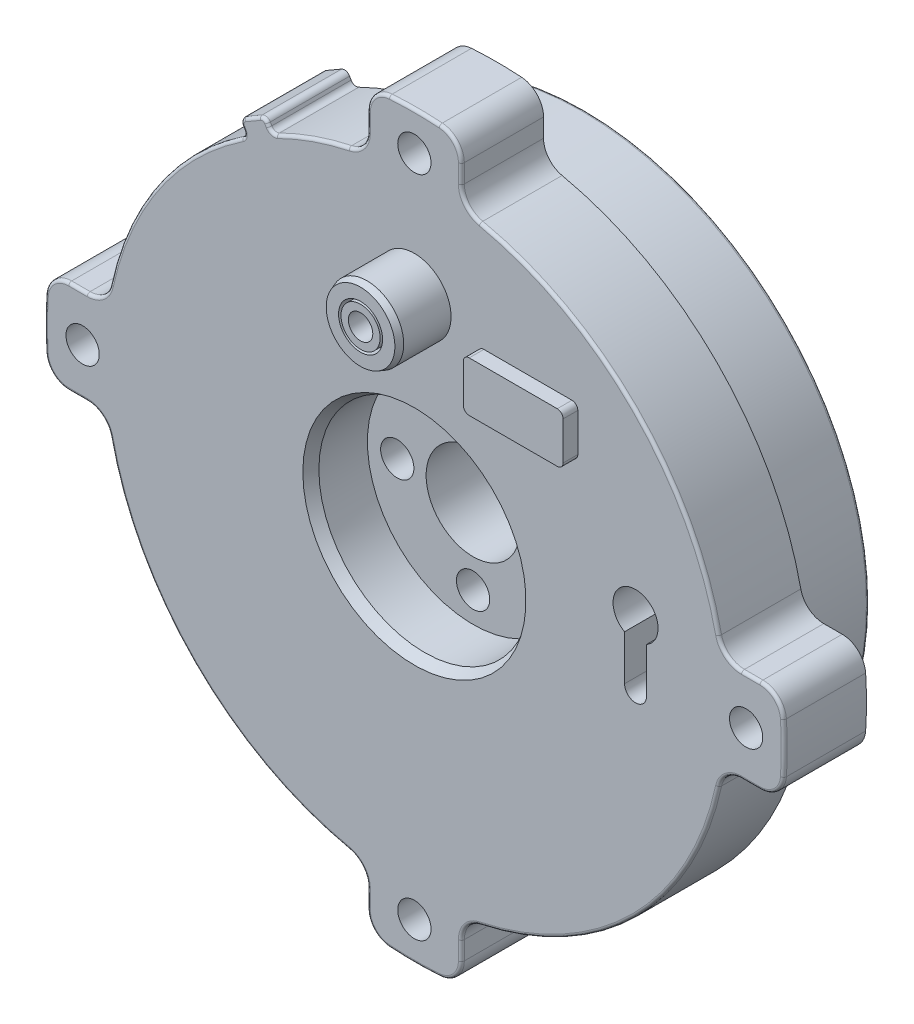
SolidWorks part; units mm, degrees
note: The reader was unsure of these and kept them because the rebuilt part matched: shared geometry of "草图4<7>", "草图4<3>".
other "l7r主轴" parameters "D2"=11, "D1"=38, "D3"=10, "D4"=11, "D5"=20, "D6"=5.8774, "D7"=5.7465, "D8"=5, "D9"=7, "D10"=8, "D11"=4, "D12"=22.25, "D13"=24.25, "D14"=5, "D15"=8.3333, "D16"=22.4267, "D17"=8, "D18"=7, "D19"=22, "4"=25.4, "通孔孔直径"=2.8333, "通孔孔深度"=11.5833, "柱形沉头孔直径"=5, "柱形沉头孔深度"=2.5
ref_plane "前视基准面" through (0, 0, 0) normal (0, 0, 1) x (1, 0, 0)
ref_plane "上视基准面" through (0, 0, 0) normal (0, 1, 0) x (1, 0, 0)
ref_plane "右视基准面" through (0, 0, 0) normal (1, 0, 0) x (0, 0, -1)
ref_plane "基准面1" through (-15, 0, 0) normal (-1, 0, 0) x (0, 0, 1)
sketch "草图29" plane through (0, 0, 0) normal (1, 0, 0) x (0, 0, -1)
  line L0 (5, 24.25) -> (5, 22.25)
  line L1 (17.875, 0) -> (-17.875, 0) construction
  line L2 (5, 22.25) -> (13, 22.25)
  line L3 (13, 22.25) -> (13, 4)
  line L6 (13, 4) -> (27, 4)
  line L7 (13, 22.25) -> (18, 22.25)
  line L8 (18, 8.3333) -> (13, 8.3333)
  line L17 (0, 0) -> (50, 0) construction
  line L18 (27, 4) -> (27, 8.3333)
  line L19 (27, 8.3333) -> (18, 8.3333)
  line L20 (18, 8.3333) -> (18, 24.25)
  line L21 (18, 24.25) -> (5, 24.25)
  dimension "D1" = 13
  dimension "D2" = 22
  dimension "D3" = 50
  dimension "D4" = 4
  dimension "D6" = 22.25
  dimension "D7" = 24.25
  dimension "D8" = 8
  dimension "D5" = 8.3333
  dimension "D9" = 5
sketch "草图6" plane through (-15, 0, 0) normal (1, 0, 0) x (0, 0, -1)
  line L0 (0, 0) -> (15.2887, 0)
  line L1 (15.2887, 0) -> (15, 0.5)
  line L2 (15, 0.5) -> (0, 0.5)
  line L3 (0, 0.5) -> (0, 0)
  line L4 (0, 34.65) -> (0, -34.65) construction
  dimension "D1" = 15
  dimension "D2" = 60
  dimension "D3" = 0.5
sketch "草图2" plane through (0, 0, 0) normal (1, 0, 0) x (0, 0, -1)
  line L0 (0, 26.5) -> (0, 4)
  line L6 (7, 24.25) -> (7, 26.5)
  line L7 (7, 26.5) -> (0, 26.5)
  line L10 (10, 10.4167) -> (23, 10.4167)
  line L11 (5, 15.4167) -> (5, 22.25)
  line L23 (7, 24.25) -> (14.5, 24.25)
  line L24 (14.5, 24.25) -> (14.5, 22.25)
  line L25 (14.5, 22.25) -> (5, 22.25)
  line L27 (-40.8092, 0) -> (40.8092, 0) construction
  line L28 (5, 15.4167) -> (10, 15.4167)
  line L29 (10, 15.4167) -> (10, 10.4167)
  line L34 (0, 4) -> (23, 4)
  line L35 (23, 10.4167) -> (23, 4)
  dimension "D3" = 7
  dimension "D5" = 5
  dimension "D16" = 14.5
  dimension "D4" = 24.25
  dimension "D17" = 22.25
  dimension "D18" = 26.5
  dimension "D2" = 23
  dimension "D6" = 4
  dimension "D19" = 10.4167
  dimension "D8" = 10
revolve "旋转1" add sketch "草图2" angle 360 about L27
sketch "草图7" plane through (0, 0, 0) normal (0, 0, 1) x (1, 0, 0)
  circle A0 centre (0, 0) radius 9
  dimension "D1" = 18
extrude "切除-拉伸1" cut sketch "草图7" against normal blind 5
sketch "草图11" plane through (0, 0, 0) normal (0, 0, 1) x (1, 0, 0)
  line L0 (18.8333, 3.5884) -> (18.8333, 1.9167) construction
  line L1 (17.8958, 1.9167) -> (19.7708, 1.9167) construction
  line L2 (19.7708, 1.9167) -> (19.7708, -1.9167)
  line L3 (17.8958, 1.9167) -> (17.8958, -1.9167)
  line L4 (19.7708, -1.9167) -> (17.8958, -1.9167) construction
  line L5 (15.4167, 0) -> (22.25, 0) construction
  line L6 (18.8333, 1.9167) -> (18.8333, -1.9167) construction
  arc A0 (19.7708, 1.9167) -> (17.8958, 1.9167) centre (18.8333, 3.5884) ccw
  arc A1 (17.8958, -1.9167) -> (19.7708, -1.9167) centre (18.8333, -1.9167) ccw
  circle A2 centre (0, 0) radius 15.4167 construction
  circle A3 centre (0, 0) radius 15.4167 construction
  circle A4 centre (0, 0) radius 22.25 construction
  circle A5 centre (0, 0) radius 22.25 construction
  point P8 (18.8333, 1.9167)
  point P14 (18.8333, 0)
  dimension "D1" = 3.8333
  dimension "D4" = 1.875
  dimension "D5" = 1.875
  dimension "D6" = 3.8333
extrude "切除-拉伸4" cut sketch "草图11" against normal up to next
sketch "草图4" plane through (0, 0, 0) normal (0, 0, 1) x (1, 0, 0)
  line L0 (0, 26.5) -> (0, 9) construction
  circle A0 centre (0, 17.75) radius 3.125
  circle A1 centre (0, 17.75) radius 1.6667
  circle A2 centre (0, 17.75) radius 1.0417
  circle A3 centre (0, 17.75) radius 1.875
  circle A4 centre (0, 0) radius 9 construction
  circle A5 centre (0, 0) radius 26.5
  circle A6 centre (0, 0) radius 26.5 construction
  circle A7 centre (0, 0) radius 9 construction
  dimension "D1" = 6.25
  dimension "D3" = 3.75
  dimension "D4" = 3.3333
  dimension "D5" = 2.0833
extrude "凸台-拉伸2" add sketch "草图4" along normal blind 4.5833 contours A0 A3 | A1 A2 | L0 A0 A3 | L0 A1 A2
extrude "凸台-拉伸6" add sketch "草图4<7>" against normal blind 4.5833 from surface at -5 contours A1 A2 starting at face at (18.8333, 0.6627, -5)
sketch "草图4<7>" plane through (0, 0, 0) normal (0, 0, 1) x (1, 0, 0) same geometry as "草图4"
extrude "切除-拉伸3" cut sketch "草图4<3>" against normal blind 10 contours A2
sketch "草图4<3>" plane through (0, 0, 0) normal (0, 0, 1) x (1, 0, 0) same geometry as "草图4"
sketch "草图9" plane through (0, 0, 0) normal (0, 0, 1) x (1, 0, 0)
  line L0 (0, 31.5) -> (0, 0) construction
  line L1 (-4, 31.245) -> (4, 31.245) construction
  line L2 (4, 29.4321) -> (4, 26.1964)
  line L3 (4, 26.1964) -> (0, 0) construction
  line L4 (-4, 29.4321) -> (-4, 26.1964)
  line L5 (29.4321, -4) -> (26.1964, -4)
  line L6 (29.4321, 4) -> (26.1964, 4)
  line L7 (-4, -29.4321) -> (-4, -26.1964)
  line L8 (4, -29.4321) -> (4, -26.1964)
  line L9 (-29.4321, 4) -> (-26.1964, 4)
  line L10 (-29.4321, -4) -> (-26.1964, -4)
  arc A0 (-2.1356, 31.4275) -> (2.1356, 31.4275) centre (0, 0) cw
  arc A1 (-2.1356, 31.4275) -> (-4, 29.4321) centre (-2, 29.4321) ccw
  arc A3 (2.1356, 31.4275) -> (4, 29.4321) centre (2, 29.4321) cw
  arc A4 (-4, 26.1964) -> (4, 26.1964) centre (0, 0) cw
  arc A5 (31.4275, 2.1356) -> (29.4321, 4) centre (29.4321, 2) ccw
  arc A6 (31.4275, 2.1356) -> (31.4275, -2.1356) centre (0, 0) cw
  arc A7 (31.4275, -2.1356) -> (29.4321, -4) centre (29.4321, -2) cw
  arc A8 (26.1964, 4) -> (26.1964, -4) centre (0, 0) cw
  arc A9 (2.1356, -31.4275) -> (4, -29.4321) centre (2, -29.4321) ccw
  arc A10 (2.1356, -31.4275) -> (-2.1356, -31.4275) centre (0, 0) cw
  arc A11 (-2.1356, -31.4275) -> (-4, -29.4321) centre (-2, -29.4321) cw
  arc A12 (4, -26.1964) -> (-4, -26.1964) centre (0, 0) cw
  arc A13 (-31.4275, -2.1356) -> (-29.4321, -4) centre (-29.4321, -2) ccw
  arc A14 (-31.4275, -2.1356) -> (-31.4275, 2.1356) centre (0, 0) cw
  arc A15 (-31.4275, 2.1356) -> (-29.4321, 4) centre (-29.4321, 2) cw
  arc A16 (-26.1964, -4) -> (-26.1964, 4) centre (0, 0) cw
  point P40 (0, 0)
  dimension "D1" = 31.5
  dimension "D4" = 2
  dimension "D2" = 8
  dimension "D3" = 26.5
  dimension "D5" = 4
extrude "凸台-拉伸3" add sketch "草图9" against normal up to surface (7 mm away) up to face at (26.5, 0, -7)
sketch "草图10" plane through (0, 0, 0) normal (0, 0, 1) x (1, 0, 0)
  line L0 (-13.85, 23.9889) -> (0, 0) construction
  line L1 (0, 0) -> (0, 35.4664) construction
  line L2 (-13.2005, 24.3639) -> (-14.4995, 23.6139)
  line L3 (-12.5175, 24.1809) -> (-12.1527, 23.5491)
  line L4 (-14.6825, 22.9309) -> (-14.3178, 22.2991)
  arc A1 (-12.1527, 23.5491) -> (-14.3178, 22.2991) centre (0, 0) ccw
  arc A2 (-14.4995, 23.6139) -> (-14.6825, 22.9309) centre (-14.2495, 23.1809) ccw
  arc A3 (-13.2005, 24.3639) -> (-12.5175, 24.1809) centre (-12.9505, 23.9309) cw
  point P10 (-13.85, 23.9889)
  point P15 (-14.9325, 23.3639)
  point P18 (-12.7675, 24.6139)
  dimension "D4" = 53
  dimension "D5" = 0.5
  dimension "D1" = 30
  dimension "D2" = 2.5
  dimension "D3" = 27.7
extrude "凸台-拉伸4" add sketch "草图10" against normal up to surface (7 mm away) up to face at (0, 0, -7)
fillet "圆角2" radius 0.5 2 edges at (-12.1527, 23.5491, -3.5) (-14.3178, 22.2991, -3.5)
sketch "草图8" plane through (0, 0, -5) normal (0, 0, 1) x (1, 0, 0)
  line L0 (-28.25, 0) -> (28.25, 0) construction
  line L1 (0, -28.25) -> (0, 28.25) construction
  circle A0 centre (0, 0) radius 6.4583 construction
  circle A1 centre (0, 0) radius 28.25 construction
  point P7 (0, 0)
  point P10 (0, 0)
  dimension "D1" = 12.9167
  dimension "D2" = 56.5
hole_wizard "M3 六角头螺钉的柱形沉头孔1" positions "草图19" profile "草图20" counterbore size "M3" standard "ISO" end condition through all
sketch "草图19" plane through (0, 0, -7) normal (0, 0, -1) x (-1, 0, 0)
  point P0 (0, 28.25)
  point P3 (28.25, 0)
  point P6 (-28.25, 0)
  point P9 (0, -28.25)
sketch "草图20" plane through (0, 28.25, -7) normal (1, 0, 0) x (0, 1, 0)
  line L0 (0, 0) -> (0, 11.5833)
  line L1 (0, 11.5833) -> (1.4167, 11.5833)
  line L3 (1.4167, 11.5833) -> (1.4167, 2.5)
  line L4 (1.4167, 2.5) -> (2.5, 2.5)
  line L5 (2.5, 2.5) -> (2.5, 0)
  line L7 (2.5, 0) -> (0, 0)
  line L11 (0, -6.35) -> (0, 107.95) construction
  dimension "通孔孔直径" = 2.8333
  dimension "柱形沉头孔直径" = 5
  dimension "柱形沉头孔深度" = 2.5
hole_wizard "M3 六角头螺钉的柱形沉头孔2" positions "草图27" profile "草图28" counterbore size "M3" standard "ISO" end condition through all
sketch "草图27" plane through (0, 0, 0) normal (0, 0, 1) x (1, 0, 0)
  line L0 (0, -28.25) -> (0, 28.25) construction
  circle A0 centre (0, 0) radius 6.4583 construction
  point P0 (0, 6.4583)
sketch "草图28" plane through (0, 6.4583, 0) normal (1, 0, 0) x (0, -1, 0)
  line L0 (0, 0) -> (0, 23)
  line L1 (0, 23) -> (1.4167, 23)
  line L3 (1.4167, 23) -> (1.4167, 2.5)
  line L4 (1.4167, 2.5) -> (2.5, 2.5)
  line L5 (2.5, 2.5) -> (2.5, 0)
  line L7 (2.5, 0) -> (0, 0)
  line L11 (0, -6.35) -> (0, 107.95) construction
  dimension "通孔孔直径" = 2.8333
  dimension "通孔孔深度" = 23
  dimension "柱形沉头孔直径" = 5
  dimension "柱形沉头孔深度" = 2.5
pattern_circular "阵列(圆周)2" count 4 over 360 about axis through (0, 0, 0) along (0, 0, 1) of "M3 六角头螺钉的柱形沉头孔2"
sketch "草图3" plane through (0, 0, 0) normal (0, 0, 1) x (1, 0, 0)
  line L0 (13.9167, 14.625) -> (5.4167, 14.625) construction
  line L1 (5.9167, 16.75) -> (13.4167, 16.75)
  line L2 (5.4167, 16.25) -> (5.4167, 13)
  line L3 (5.9167, 12.5) -> (13.4167, 12.5)
  line L4 (13.9167, 16.25) -> (13.9167, 13)
  line L5 (5.4167, 14.625) -> (-15.5609, 14.625) construction
  arc A0 (13.4167, 16.75) -> (13.9167, 16.25) centre (13.4167, 16.25) cw
  arc A1 (13.4167, 12.5) -> (13.9167, 13) centre (13.4167, 13) ccw
  arc A2 (5.4167, 13) -> (5.9167, 12.5) centre (5.9167, 13) ccw
  arc A3 (5.9167, 16.75) -> (5.4167, 16.25) centre (5.9167, 16.25) ccw
  circle A4 centre (0, 17.75) radius 3.125 construction
  circle A5 centre (0, 17.75) radius 3.125 construction
  dimension "D5" = 0.5
  dimension "D1" = 5.4167
  dimension "D2" = 13.9167
  dimension "D3" = 4.25
extrude "凸台-拉伸1" add sketch "草图3" along normal blind 1.25
chamfer "倒角1" distance 0.2 angle 70 1 edges at (3.125, 17.75, 4.5833) first distance on face at (1.875, 17.75, 4.5833)
chamfer "倒角2" distance 0.5 angle 60 1 edges at (9, 0, 0) first distance on face at (-3.3329, 5.7952, 0)
fillet "圆角5" radius 2 8 edges at (-4, 26.1964, -3.5) (4, 26.1964, -3.5) (26.1964, 4, -3.5) (26.1964, -4, -3.5) (4, -26.1964, -3.5) (-4, -26.1964, -3.5) (-26.1964, -4, -3.5) (-26.1964, 4, -3.5)
fillet "圆角4" radius 0.254 44 edges at (-21.9128, 14.9023, 0) (-14.5003, 22.3448, 0) (-14.6183, 22.8197, 0) (-14.7325, 23.3103, 0) (-13.85, 23.9889, 0) (-12.8211, 24.4139, 0) (-12.4533, 24.0697, 0) (-12.1011, 23.73, 0) (-8.723, 25.0232, 0) (10.4167, 0, -23) (22.25, 0, -14.5) (24.25, 0, -14.5) (15.4167, 0, -10) (26.6047, 4.444, 0) (28.6467, 4, 0) (30.7976, 3.4614, 0) (31.5, 0, 0) (30.7976, -3.4614, 0) (28.6467, -4, 0) (26.6047, -4.444, 0) (18.7383, -18.7383, 0) (4.444, -26.6047, 0) (4, -28.6467, 0) (3.4614, -30.7976, 0) (0, -31.5, 0) (-3.4614, -30.7976, 0) (-4, -28.6467, 0) (-4.444, -26.6047, 0) (-18.7383, -18.7383, 0) (-26.6047, -4.444, 0) (-28.6467, -4, 0) (-30.7976, -3.4614, 0) (-31.5, 0, 0) (-30.7976, 3.4614, 0) (-28.6467, 4, 0) (-26.6047, 4.444, 0) (-4.444, 26.6047, 0) (-4, 28.6467, 0) (-3.4614, 30.7976, 0) (0, 31.5, 0) (3.4614, 30.7976, 0) (4, 28.6467, 0) (4.444, 26.6047, 0) (18.7383, 18.7383, 0)
equation "\"axis1­_inner_dim\" = 72"
equation "\"axis1_outer_dim\" = 120"
equation "\"axis1_install_inner_dim\" = \"axis1_cross_roller_bear_inner_dim\""
equation "\"axis1_install_outer_dim\" = 60"
equation "\"axis1_install_shell_thick\" = \"shell_thickness_c\""
equation "\"axis1_total_len\" = 170"
equation "\"axis1to2_vertical_dim\" = 30"
equation "\"axis1_cross_roller_bear_inner_dim\" = 52"
equation "\"axis2_inner_dim\" = 40"
equation "\"axis2_outer_dim\" = 90"
equation "\"axis2_install_inner_dim\" = \"vexta_asm46aa2_install_ring_dim\""
equation "\"axis2_install_outer_dim\" = 60"
equation "\"axis2_install_shell_thick\" = \"shell_thickness_c\""
equation "\"axis2_total_len\" = 195"
equation "\"axis2_cam_tangent_weight\" = \"cam_tangent_weight\""
equation "\"axis2_inner_cam_base_rad\" = 50"
equation "\"axis2_inner_cam_lobe_dim\" = 74"
equation "\"axis2_outer_cam_base_rad\" = 45"
equation "\"axis2_outer_cam_lobe_dim\" = 69"
equation "\"axis2_side_cover_cam_base_rad\" = 47.5"
equation "\"axis2_side_cover_cam_lobe_dim\" = 71.5"
equation "\"axis2_side_cover_outer_circle_rad\" = 36"
equation "\"axis2_side_cover_inner_circle_rad\" = 32"
equation "\"axis2_side_cover_small_circle_rad\" = 27"
equation "\"axis2to7_vertical_dim\" = \"axis1to2_vertical_dim\""
equation "\"axis7_inner_dim\" = 40"
equation "\"axis7_outer_dim\" = 94"
equation "\"axis7_install_inner_dim\" = \"vexta_asm46aa2_install_ring_dim\""
equation "\"axis7_install_outer_dim\" = 60"
equation "\"axis7_install_shell_thick\" = \"shell_thickness_c\""
equation "\"axis7_total_len\" = 255"
equation "\"axis7to3_vertical_dim\" = 40.5"
equation "\"axis3_inner_dim\" = 30"
equation "\"axis3_outer_dim\" = 72"
equation "\"axis3_install_inner_dim\" = \"vexta_asm46aa2_install_ring_dim\""
equation "\"axis3_install_outer_dim\" = 60"
equation "\"axis3_install_shell_thick\" = \"shell_thickness_c\""
equation "\"axis3_total_len\" = 195"
equation "\"axis3_cam_tangent_weight\" = \"cam_tangent_weight\""
equation "\"axis3_inner_cam_base_rad\" = 50"
equation "\"axis3_inner_cam_lobe_dim\" = 69"
equation "\"axis3_outer_cam_base_rad\" = 47.5"
equation "\"axis3_outer_cam_lobe_dim\" = 66.5"
equation "\"axis3_side_cover_cam_base_rad\" = 45"
equation "\"axis3_side_cover_cam_lobe_dim\" = 64"
equation "\"axis3_side_cover_outer_circle_rad\" = 25"
equation "\"axis3_side_cover_inner_circle_rad\" = 17.5"
equation "\"axis3_side_cover_small_circle_rad\" = 13"
equation "\"axis3to4_vertical_dim\" = \"axis7to3_vertical_dim\""
equation "\"axis4_inner_dim\" = 30"
equation "\"axis4_outer_dim\" = 75"
equation "\"axis4_install_inner_dim\" = \"vexta_arm24sak_install_ring_dim\" "
equation "\"axis4_install_outer_dim\" = 60"
equation "\"axis4_install_shell_thick\" = \"shell_thickness_c\""
equation "\"axis4_total_len\" = 265"
equation "\"axis4to5_vertical_dim\" = 27"
equation "\"axis5_inner_dim\" = 30"
equation "\"axis5_outer_dim\" = 50"
equation "\"axis5_install_inner_dim\" = \"vexta_arm24sak_install_ring_dim\""
equation "\"axis5_install_outer_dim\" = 60"
equation "\"axis5_install_shell_thick\" = \"shell_thickness_c\""
equation "\"axis5_total_len\" =160"
equation "\"axis5_cam_tangent_weight\" = \"cam_tangent_weight\""
equation "\"axis5_inner_cam_base_rad\" = 34"
equation "\"axis5_inner_cam_lobe_dim\" = 54"
equation "\"axis5_outer_cam_base_rad\" = 31"
equation "\"axis5_outer_cam_lobe_dim\" = 51"
equation "\"axis5_side_cover_cam_base_rad\" = 30"
equation "\"axis5_side_cover_cam_lobe_dim\" = 50"
equation "\"axis5_side_cover_outer_circle_rad\" = 22"
equation "\"axis5_side_cover_inner_circle_rad\" = 14"
equation "\"axis5_side_cover_small_circle_rad\" = 11"
equation "\"axis5to6_vertical_dim\" = \"axis4to5_vertical_dim\""
equation "\"axis6_inner_dim\" = 20"
equation "\"axis6_outer_dim\" = 48.5"
equation "\"axis6_install_inner_dim\" = \"vexta_arm24sak_install_ring_dim\""
equation "\"axis6_install_outer_dim\" = 60"
equation "\"axis6_install_shell_thick\" = \"shell_thickness_c\""
equation "\"axis6_total_len\" = 36"
equation "\"cam_tangent_weight\" = 5"
equation "\"trapezoidal_circle_tangent_weight_center\" = 10"
equation "\"trapezoidal_circle_tangent_weight_edge\" = 10"
equation "\"shell_thickness_a\" = 2"
equation "\"shell_thickness_b\" = 4"
equation "\"shell_thickness_c\" = 6"
equation "\"inner_shell_thick\" = 2"
equation "\"outer_shell_thick\" = 4"
equation "\"shell_thick_adjust\" = 0"
equation "\"fit_tolerance_adjust_a\" = 0.2"
equation "\"fit_tolerance_adjust_b\" = 0.1"
equation "\"fit_tolerance_adjust_c\" = 0.5"
equation "\"m2.5_screw_hole_depth\" = 10"
equation "\"m2.5_screw_through_hole_outer_depth\" = 2"
equation "\"m2.5_screw_through_hole_inner_dim\" = 2.9"
equation "\"m2.5_screw_through_hole_outer_dim\" = 5.5"
equation "\"m2.5_screw_self_tapping_hole_dim\" = 2.1"
equation "\"m3_screw_hole_depth\" = 10"
equation "\"m3_screw_through_hole_outer_depth\" = 3"
equation "\"m3_screw_through_hole_inner_dim\" = 3.4"
equation "\"m3_screw_through_hole_outer_dim\" = 6"
equation "\"m3_screw_self_tapping_hole_dim\" = 2.5"
equation "\"m3_screw_self_tapping_hole_depth\" = 10"
equation "\"m4_screw_hole_depth\" = 10"
equation "\"m4_screw_through_hole_outer_depth\" = 4.5"
equation "\"m4_screw_through_hole_inner_dim\" = 4.5"
equation "\"m4_screw_through_hole_outer_dim\" = 7.5"
equation "\"m4_screw_self_tapping_hole_dim\" = 3.5"
equation "\"m4_screw_self_tapping_hole_depth\" = 10"
equation "\"vexta_asm46aa2_install_ring_dim\" = 37.6"
equation "\"vexta_asm46aa2_install_ring_thickness\" = 2"
equation "\"vexta_asm46aa2_install_base_m4_screw_depth\" = 9"
equation "\"vexta_asm46aa2_install_ring_m3_screw_depth\" = 6"
equation "\"vexta_asm46aa2_h_gear_install_dim\" = 20.5"
equation "\"vexta_asm46aa2_h_gear_install_m3_screw_depth\" = 5"
equation "\"vexta_asm46aa2_axis_dim\" = 10"
equation "\"vexta_arm24sak_install_ring_dim\" = 29"
equation "\"vexta_arm24sak_install_ring_thickness\" = 2.5"
equation "\"vexta_arm24sak_install_base_m3_screw_depth\" = 7"
equation "\"vexta_arm24sak_install_ring_m3_screw_depth\" = 4.5"
equation "\"vexta_arm24sak_h_gear_install_dim\" = 15.5"
equation "\"vexta_arm24sak_h_gear_install_m3_screw_depth\" = 5"
equation "\"vexta_arm24sak_axis_dim\" = 8"
equation "\"enabot_v3_scale_factor\" = 1.2"
equation "\"D5@草图29\"=(\"axis6_inner_dim\") / 2 / \"enabot_v3_scale_factor\""
equation "\"D19@草图2\"=(\"vexta_arm24sak_install_ring_dim\" - \"shell_thickness_b\" ) / 2 / \"enabot_v3_scale_factor\""
equation "\"柱形沉头孔直径@草图20\"= \"m3_screw_through_hole_outer_dim\" / \"enabot_v3_scale_factor\""
equation "\"柱形沉头孔深度@草图20\"= \"m3_screw_through_hole_outer_depth\" / \"enabot_v3_scale_factor\""
equation "\"通孔孔直径@草图20\"= \"m3_screw_through_hole_inner_dim\" / \"enabot_v3_scale_factor\""
equation "\"柱形沉头孔直径@草图28\"= \"m3_screw_through_hole_outer_dim\" / \"enabot_v3_scale_factor\""
equation "\"通孔孔直径@草图28\"= \"m3_screw_through_hole_inner_dim\" / \"enabot_v3_scale_factor\""
equation "\"柱形沉头孔深度@草图28\"= \"m3_screw_through_hole_outer_depth\" / \"enabot_v3_scale_factor\""
equation "\"D1@草图8\"= \"vexta_arm24sak_h_gear_install_dim\" / \"enabot_v3_scale_factor\""
equation "\"D5@草图4\"= 2.50 / \"enabot_v3_scale_factor\""
equation "\"D4@草图4\"= 4.00 / \"enabot_v3_scale_factor\""
equation "\"D3@草图4\"= 4.50 / \"enabot_v3_scale_factor\""
equation "\"D1@草图4\"= 7.50  / \"enabot_v3_scale_factor\""
equation "\"D1@草图3\"= 6.50 / \"enabot_v3_scale_factor\""
equation "\"D2@草图3\"= 16.7 / \"enabot_v3_scale_factor\""
equation "\"D3@草图3\"= 5.10 / \"enabot_v3_scale_factor\""
equation "\"D1@凸台-拉伸1\"= 1.5  / \"enabot_v3_scale_factor\""
equation "\"D1@草图11\"=4.60 / \"enabot_v3_scale_factor\""
equation "\"D6@草图11\"=\"D1@草图11\""
equation "\"D5@草图11\"= 2.25 / \"enabot_v3_scale_factor\""
equation "\"D4@草图11\"=2.25 / \"enabot_v3_scale_factor\""
equation "\"D1@凸台-拉伸2\"= 5.50 / \"enabot_v3_scale_factor\""
equation "\"D1@凸台-拉伸6\"= 5.50 / \"enabot_v3_scale_factor\""
